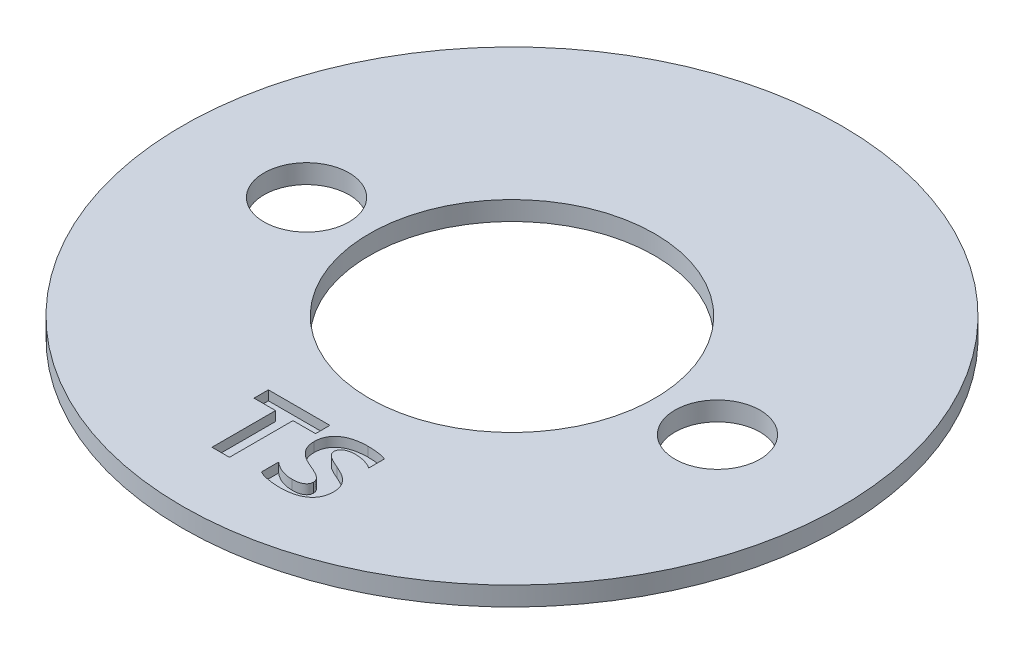
SolidWorks part; units mm, degrees
material "ABS"
ref_plane "Front Plane" through (0, 0, 0) normal (0, 0, 1) x (1, 0, 0)
ref_plane "Top Plane" through (0, 0, 0) normal (0, 1, 0) x (1, 0, 0)
ref_plane "Right Plane" through (0, 0, 0) normal (1, 0, 0) x (0, 0, -1)
sketch "Sketch1" plane through (0, 0, 0) normal (0, 1, 0) x (1, 0, 0)
  circle A0 centre (0, 0) radius 27.5
  dimension "D1" = 55
extrude "Boss-Extrude1" add sketch "Sketch1" along normal blind 1.5875
sketch "Sketch4" plane through (0, 0, 0) normal (0, -1, 0) x (1, 0, 0)
  line L0 (-17.145, 0) -> (17.145, 0) construction
  circle A4 centre (-17.145, 0) radius 3.55
  circle A5 centre (0, 0) radius 11.9062
  circle A6 centre (17.145, 0) radius 3.55
  dimension "D1" = 7.1
  dimension "D2" = 23.8125
  dimension "D3" = 34.29
extrude "Cut-Extrude2" cut sketch "Sketch4" against normal through all
sketch "Sketch2" plane through (0, 1.5875, 0) normal (0, 1, 0) x (1, 0, 0)
  line L0 (-5, -22) -> (5, -22) construction
  line L1 (0, 0) -> (0, -22) construction
  text T0 "TS" font "Nirmala UI" height 6.5
  dimension "D1" = 10
  dimension "D2" = 22
extrude "Cut-Extrude1" cut sketch "Sketch2" against normal offset from surface (0.7938 mm away) 0.7937 up to face at (-17.145, 0, -3.55)
